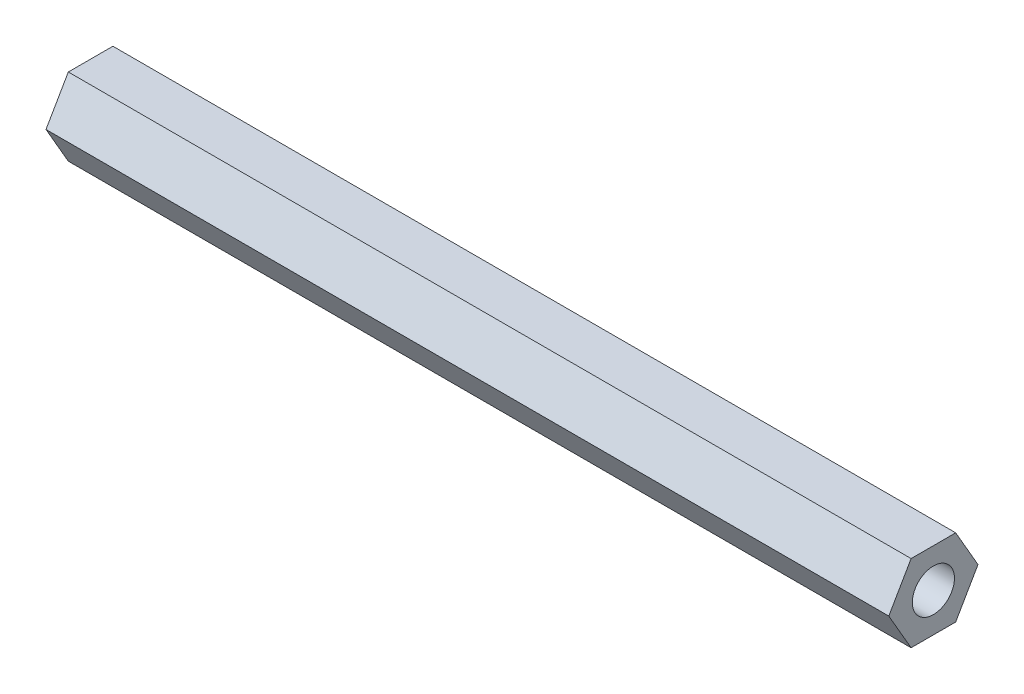
SolidWorks part; units mm, degrees
ref_plane "Front Plane" through (0, 0, 0) normal (0, 0, 1) x (1, 0, 0)
ref_plane "Top Plane" through (0, 0, 0) normal (0, 1, 0) x (1, 0, 0)
ref_plane "Right Plane" through (0, 0, 0) normal (1, 0, 0) x (0, 0, -1)
sketch "Hex Sketch" plane through (0, 0, 0) normal (1, 0, 0) x (0, 0, -1)
  line L0 (3.1754, 0) -> (1.5877, 2.75)
  line L1 (1.5877, 2.75) -> (-1.5877, 2.75)
  line L2 (-1.5877, 2.75) -> (-3.1754, 0)
  line L3 (-3.1754, 0) -> (-1.5877, -2.75)
  line L4 (-1.5877, -2.75) -> (1.5877, -2.75)
  line L5 (1.5877, -2.75) -> (3.1754, 0)
extrude "Hex" add sketch "Hex Sketch" along normal blind 60
ref_axis "Engine Axis" through (63, 0, 0) along (-1, 0, 0)
sketch "Bore Sketch" plane through (0, 0, 0) normal (0, 0, 1) x (1, 0, 0)
  line L0 (-400, 0) -> (400, 0) construction
  line L1 (-1, 0) -> (61, 0)
  line L2 (61, 0) -> (61, 1.5)
  line L3 (61, 1.5) -> (-1, 1.5)
  line L4 (-1, 1.5) -> (-1, 0)
revolve "Bore" cut sketch "Bore Sketch" angle 360 about L0
